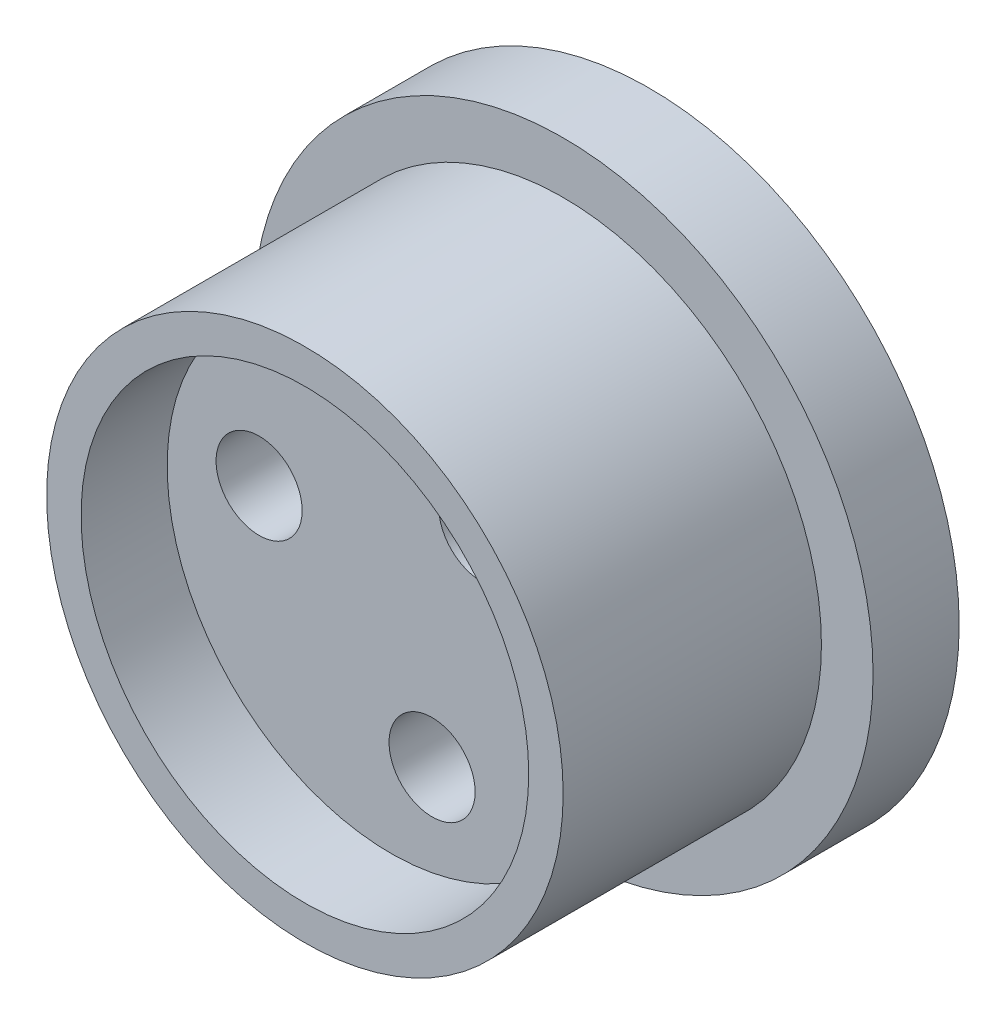
SolidWorks part; units mm, degrees
ref_plane "Front Plane" through (0, 0, 0) normal (0, 0, 1) x (1, 0, 0)
ref_plane "Top Plane" through (0, 0, 0) normal (0, 1, 0) x (1, 0, 0)
ref_plane "Right Plane" through (0, 0, 0) normal (1, 0, 0) x (0, 0, -1)
sketch "Sketch1" plane through (0, 0, 0) normal (0, 0, 1) x (1, 0, 0)
  circle A0 centre (0, 0) radius 18
  circle A1 centre (0, 0) radius 15
  circle A2 centre (0, 0) radius 13
  dimension "D1" = 36
  dimension "D2" = 30
  dimension "D3" = 26
extrude "Boss-Extrude1" add sketch "Sketch1" along normal blind 5 contours A0 A1 region at (-17.4909, 0, 0)
extrude "Boss-Extrude2" add sketch "Sketch1<3>" along normal blind 20 contours A1 A2 region at (-14.5757, 0, 0)
sketch "Sketch1<3>" plane through (0, 0, 0) normal (0, 0, 1) x (1, 0, 0) same geometry as "Sketch1"
extrude "Boss-Extrude3" add sketch "Sketch1<4>" along normal blind 15 contours A2 region at (0, 0, 0)
sketch "Sketch1<4>" plane through (0, 0, 0) normal (0, 0, 1) x (1, 0, 0) same geometry as "Sketch1"
sketch "Sketch2" plane through (0, 0, 15) normal (0, 0, 1) x (1, 0, 0)
  circle A0 centre (-7.66, 1.6664) radius 2.5
  circle A1 centre (5.2731, 5.8006) radius 2.5
  circle A2 centre (2.3869, -7.467) radius 2.5
  dimension "D3" = 5
  dimension "D2" = 7.66
  dimension "D1" = 3
extrude "Cut-Extrude1" cut sketch "Sketch2" against normal through all
